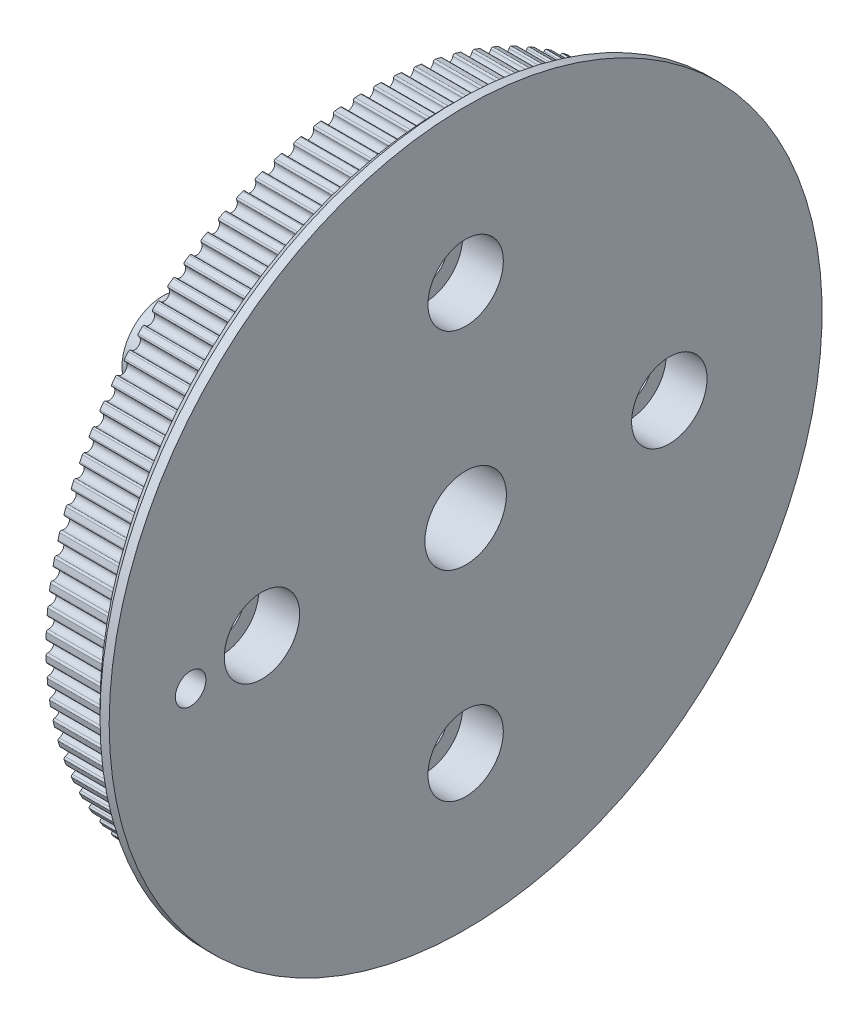
SolidWorks part; units mm, degrees
ref_plane "Front Plane" through (0, 0, 0) normal (0, 0, 1) x (1, 0, 0)
ref_plane "Top Plane" through (0, 0, 0) normal (0, 1, 0) x (1, 0, 0)
ref_plane "Right Plane" through (0, 0, 0) normal (1, 0, 0) x (0, 0, -1)
sketch "Sketch1" plane through (0, 0, 0) normal (1, 0, 0) x (0, 0, -1)
  circle A0 centre (0, 0) radius 31.6
  circle A1 centre (0, 0) radius 4
  dimension "D1" = 63.2
  dimension "D2" = 8
extrude "Boss-Extrude1" add sketch "Sketch1" along normal blind 7.7
sketch "Sketch2" plane through (0, 0, 0) normal (1, 0, 0) x (0, 0, -1)
  circle A0 centre (0, 0) radius 31.39 construction
  circle A1 centre (0, 31.39) radius 0.55
  circle A2 centre (0, 0) radius 31.39 construction
  circle A3 centre (1.971, 31.3281) radius 0.55
  circle A4 centre (0, 0) radius 31.39 construction
  circle A5 centre (3.9342, 31.1425) radius 0.55
  circle A6 centre (0, 0) radius 31.39 construction
  circle A7 centre (5.8819, 30.834) radius 0.55
  circle A8 centre (0, 0) radius 31.39 construction
  circle A9 centre (7.8064, 30.4038) radius 0.55
  circle A10 centre (0, 0) radius 31.39 construction
  circle A11 centre (9.7, 29.8537) radius 0.55
  circle A12 centre (0, 0) radius 31.39 construction
  circle A13 centre (11.5554, 29.1857) radius 0.55
  circle A14 centre (0, 0) radius 31.39 construction
  circle A15 centre (13.3652, 28.4025) radius 0.55
  circle A16 centre (0, 0) radius 31.39 construction
  circle A17 centre (15.1222, 27.5073) radius 0.55
  circle A18 centre (0, 0) radius 31.39 construction
  circle A19 centre (16.8196, 26.5035) radius 0.55
  circle A20 centre (0, 0) radius 31.39 construction
  circle A21 centre (18.4506, 25.395) radius 0.55
  circle A22 centre (0, 0) radius 31.39 construction
  circle A23 centre (20.0087, 24.1864) radius 0.55
  circle A24 centre (0, 0) radius 31.39 construction
  circle A25 centre (21.4879, 22.8823) radius 0.55
  circle A26 centre (0, 0) radius 31.39 construction
  circle A27 centre (22.8823, 21.4879) radius 0.55
  circle A28 centre (0, 0) radius 31.39 construction
  circle A29 centre (24.1864, 20.0087) radius 0.55
  circle A30 centre (0, 0) radius 31.39 construction
  circle A31 centre (25.395, 18.4506) radius 0.55
  circle A32 centre (0, 0) radius 31.39 construction
  circle A33 centre (26.5035, 16.8196) radius 0.55
  circle A34 centre (0, 0) radius 31.39 construction
  circle A35 centre (27.5073, 15.1222) radius 0.55
  circle A36 centre (0, 0) radius 31.39 construction
  circle A37 centre (28.4025, 13.3652) radius 0.55
  circle A38 centre (0, 0) radius 31.39 construction
  circle A39 centre (29.1857, 11.5554) radius 0.55
  circle A40 centre (0, 0) radius 31.39 construction
  circle A41 centre (29.8537, 9.7) radius 0.55
  circle A42 centre (0, 0) radius 31.39 construction
  circle A43 centre (30.4038, 7.8064) radius 0.55
  circle A44 centre (0, 0) radius 31.39 construction
  circle A45 centre (30.834, 5.8819) radius 0.55
  circle A46 centre (0, 0) radius 31.39 construction
  circle A47 centre (31.1425, 3.9342) radius 0.55
  circle A48 centre (0, 0) radius 31.39 construction
  circle A49 centre (31.3281, 1.971) radius 0.55
  circle A50 centre (0, 0) radius 31.39 construction
  circle A51 centre (31.39, 0) radius 0.55
  circle A52 centre (0, 0) radius 31.39 construction
  circle A53 centre (31.3281, -1.971) radius 0.55
  circle A54 centre (0, 0) radius 31.39 construction
  circle A55 centre (31.1425, -3.9342) radius 0.55
  circle A56 centre (0, 0) radius 31.39 construction
  circle A57 centre (30.834, -5.8819) radius 0.55
  circle A58 centre (0, 0) radius 31.39 construction
  circle A59 centre (30.4038, -7.8064) radius 0.55
  circle A60 centre (0, 0) radius 31.39 construction
  circle A61 centre (29.8537, -9.7) radius 0.55
  circle A62 centre (0, 0) radius 31.39 construction
  circle A63 centre (29.1857, -11.5554) radius 0.55
  circle A64 centre (0, 0) radius 31.39 construction
  circle A65 centre (28.4025, -13.3652) radius 0.55
  circle A66 centre (0, 0) radius 31.39 construction
  circle A67 centre (27.5073, -15.1222) radius 0.55
  circle A68 centre (0, 0) radius 31.39 construction
  circle A69 centre (26.5035, -16.8196) radius 0.55
  circle A70 centre (0, 0) radius 31.39 construction
  circle A71 centre (25.395, -18.4506) radius 0.55
  circle A72 centre (0, 0) radius 31.39 construction
  circle A73 centre (24.1864, -20.0087) radius 0.55
  circle A74 centre (0, 0) radius 31.39 construction
  circle A75 centre (22.8823, -21.4879) radius 0.55
  circle A76 centre (0, 0) radius 31.39 construction
  circle A77 centre (21.4879, -22.8823) radius 0.55
  circle A78 centre (0, 0) radius 31.39 construction
  circle A79 centre (20.0087, -24.1864) radius 0.55
  circle A80 centre (0, 0) radius 31.39 construction
  circle A81 centre (18.4506, -25.395) radius 0.55
  circle A82 centre (0, 0) radius 31.39 construction
  circle A83 centre (16.8196, -26.5035) radius 0.55
  circle A84 centre (0, 0) radius 31.39 construction
  circle A85 centre (15.1222, -27.5073) radius 0.55
  circle A86 centre (0, 0) radius 31.39 construction
  circle A87 centre (13.3652, -28.4025) radius 0.55
  circle A88 centre (0, 0) radius 31.39 construction
  circle A89 centre (11.5554, -29.1857) radius 0.55
  circle A90 centre (0, 0) radius 31.39 construction
  circle A91 centre (9.7, -29.8537) radius 0.55
  circle A92 centre (0, 0) radius 31.39 construction
  circle A93 centre (7.8064, -30.4038) radius 0.55
  circle A94 centre (0, 0) radius 31.39 construction
  circle A95 centre (5.8819, -30.834) radius 0.55
  circle A96 centre (0, 0) radius 31.39 construction
  circle A97 centre (3.9342, -31.1425) radius 0.55
  circle A98 centre (0, 0) radius 31.39 construction
  circle A99 centre (1.971, -31.3281) radius 0.55
  circle A100 centre (0, 0) radius 31.39 construction
  circle A101 centre (0, -31.39) radius 0.55
  circle A102 centre (0, 0) radius 31.39 construction
  circle A103 centre (-1.971, -31.3281) radius 0.55
  circle A104 centre (0, 0) radius 31.39 construction
  circle A105 centre (-3.9342, -31.1425) radius 0.55
  circle A106 centre (0, 0) radius 31.39 construction
  circle A107 centre (-5.8819, -30.834) radius 0.55
  circle A108 centre (0, 0) radius 31.39 construction
  circle A109 centre (-7.8064, -30.4038) radius 0.55
  circle A110 centre (0, 0) radius 31.39 construction
  circle A111 centre (-9.7, -29.8537) radius 0.55
  circle A112 centre (0, 0) radius 31.39 construction
  circle A113 centre (-11.5554, -29.1857) radius 0.55
  circle A114 centre (0, 0) radius 31.39 construction
  circle A115 centre (-13.3652, -28.4025) radius 0.55
  circle A116 centre (0, 0) radius 31.39 construction
  circle A117 centre (-15.1222, -27.5073) radius 0.55
  circle A118 centre (0, 0) radius 31.39 construction
  circle A119 centre (-16.8196, -26.5035) radius 0.55
  circle A120 centre (0, 0) radius 31.39 construction
  circle A121 centre (-18.4506, -25.395) radius 0.55
  circle A122 centre (0, 0) radius 31.39 construction
  circle A123 centre (-20.0087, -24.1864) radius 0.55
  circle A124 centre (0, 0) radius 31.39 construction
  circle A125 centre (-21.4879, -22.8823) radius 0.55
  circle A126 centre (0, 0) radius 31.39 construction
  circle A127 centre (-22.8823, -21.4879) radius 0.55
  circle A128 centre (0, 0) radius 31.39 construction
  circle A129 centre (-24.1864, -20.0087) radius 0.55
  circle A130 centre (0, 0) radius 31.39 construction
  circle A131 centre (-25.395, -18.4506) radius 0.55
  circle A132 centre (0, 0) radius 31.39 construction
  circle A133 centre (-26.5035, -16.8196) radius 0.55
  circle A134 centre (0, 0) radius 31.39 construction
  circle A135 centre (-27.5073, -15.1222) radius 0.55
  circle A136 centre (0, 0) radius 31.39 construction
  circle A137 centre (-28.4025, -13.3652) radius 0.55
  circle A138 centre (0, 0) radius 31.39 construction
  circle A139 centre (-29.1857, -11.5554) radius 0.55
  circle A140 centre (0, 0) radius 31.39 construction
  circle A141 centre (-29.8537, -9.7) radius 0.55
  circle A142 centre (0, 0) radius 31.39 construction
  circle A143 centre (-30.4038, -7.8064) radius 0.55
  circle A144 centre (0, 0) radius 31.39 construction
  circle A145 centre (-30.834, -5.8819) radius 0.55
  circle A146 centre (0, 0) radius 31.39 construction
  circle A147 centre (-31.1425, -3.9342) radius 0.55
  circle A148 centre (0, 0) radius 31.39 construction
  circle A149 centre (-31.3281, -1.971) radius 0.55
  circle A150 centre (0, 0) radius 31.39 construction
  circle A151 centre (-31.39, 0) radius 0.55
  circle A152 centre (0, 0) radius 31.39 construction
  circle A153 centre (-31.3281, 1.971) radius 0.55
  circle A154 centre (0, 0) radius 31.39 construction
  circle A155 centre (-31.1425, 3.9342) radius 0.55
  circle A156 centre (0, 0) radius 31.39 construction
  circle A157 centre (-30.834, 5.8819) radius 0.55
  circle A158 centre (0, 0) radius 31.39 construction
  circle A159 centre (-30.4038, 7.8064) radius 0.55
  circle A160 centre (0, 0) radius 31.39 construction
  circle A161 centre (-29.8537, 9.7) radius 0.55
  circle A162 centre (0, 0) radius 31.39 construction
  circle A163 centre (-29.1857, 11.5554) radius 0.55
  circle A164 centre (0, 0) radius 31.39 construction
  circle A165 centre (-28.4025, 13.3652) radius 0.55
  circle A166 centre (0, 0) radius 31.39 construction
  circle A167 centre (-27.5073, 15.1222) radius 0.55
  circle A168 centre (0, 0) radius 31.39 construction
  circle A169 centre (-26.5035, 16.8196) radius 0.55
  circle A170 centre (0, 0) radius 31.39 construction
  circle A171 centre (-25.395, 18.4506) radius 0.55
  circle A172 centre (0, 0) radius 31.39 construction
  circle A173 centre (-24.1864, 20.0087) radius 0.55
  circle A174 centre (0, 0) radius 31.39 construction
  circle A175 centre (-22.8823, 21.4879) radius 0.55
  circle A176 centre (0, 0) radius 31.39 construction
  circle A177 centre (-21.4879, 22.8823) radius 0.55
  circle A178 centre (0, 0) radius 31.39 construction
  circle A179 centre (-20.0087, 24.1864) radius 0.55
  circle A180 centre (0, 0) radius 31.39 construction
  circle A181 centre (-18.4506, 25.395) radius 0.55
  circle A182 centre (0, 0) radius 31.39 construction
  circle A183 centre (-16.8196, 26.5035) radius 0.55
  circle A184 centre (0, 0) radius 31.39 construction
  circle A185 centre (-15.1222, 27.5073) radius 0.55
  circle A186 centre (0, 0) radius 31.39 construction
  circle A187 centre (-13.3652, 28.4025) radius 0.55
  circle A188 centre (0, 0) radius 31.39 construction
  circle A189 centre (-11.5554, 29.1857) radius 0.55
  circle A190 centre (0, 0) radius 31.39 construction
  circle A191 centre (-9.7, 29.8537) radius 0.55
  circle A192 centre (0, 0) radius 31.39 construction
  circle A193 centre (-7.8064, 30.4038) radius 0.55
  circle A194 centre (0, 0) radius 31.39 construction
  circle A195 centre (-5.8819, 30.834) radius 0.55
  circle A196 centre (0, 0) radius 31.39 construction
  circle A197 centre (-3.9342, 31.1425) radius 0.55
  circle A198 centre (0, 0) radius 31.39 construction
  circle A199 centre (-1.971, 31.3281) radius 0.55
  point P305 (0, 0)
  dimension "D1" = 62.78
  dimension "D2" = 1.1
  dimension "D3" = 100
extrude "Cut-Extrude1" cut sketch "Sketch2" along normal up to surface (7.7 mm away) up to face at (7.7, 0, -31.6)
fillet "Fillet1" radius 0.16 200 edges at (3.85, 31.5959, 0.51) (3.85, 31.5656, 1.4749) (3.85, 21.2571, -23.3815) (3.85, 22.6833, -22.0007) (3.85, 22.0007, -22.6833) (3.85, 20.5329, -24.02) (3.85, 19.747, -24.6701) (3.85, 18.9842, -25.2618) (3.85, 18.159, -25.8614) (3.85, 17.3605, -26.404) (3.85, 16.4993, -26.9506) (3.85, 15.6684, -27.442) (3.85, 14.7745, -27.9334) (3.85, 13.9143, -28.3717) (3.85, 12.9914, -28.806) (3.85, 12.1054, -29.1894) (3.85, 23.3815, -21.2571) (3.85, 24.02, -20.5329) (3.85, 24.6701, -19.747) (3.85, 25.2618, -18.9842) (3.85, 25.8614, -18.159) (3.85, 26.404, -17.3605) (3.85, 26.9506, -16.4993) (3.85, 27.442, -15.6684) (3.85, 27.9334, -14.7745) (3.85, 28.3717, -13.9143) (3.85, 28.806, -12.9914) (3.85, 29.1894, -12.1054) (3.85, 29.5649, -11.157) (3.85, 29.8919, -10.2487) (3.85, 30.2071, -9.2786) (3.85, 30.4764, -8.3516) (3.85, 30.7301, -7.3636) (3.85, 30.9407, -6.4215) (3.85, 31.1318, -5.4195) (3.85, 31.2828, -4.466) (3.85, 31.4107, -3.454) (3.85, 31.5015, -2.4929) (3.85, 31.5656, -1.4749) (3.85, 31.5959, -0.51) (3.85, 31.5015, 2.4929) (3.85, 31.4107, 3.454) (3.85, 31.2828, 4.466) (3.85, 31.1318, 5.4195) (3.85, 30.9407, 6.4215) (3.85, 30.7301, 7.3636) (3.85, 30.4764, 8.3516) (3.85, 30.2071, 9.2786) (3.85, 29.8919, 10.2487) (3.85, 29.5649, 11.157) (3.85, 29.1894, 12.1054) (3.85, 28.806, 12.9914) (3.85, 28.3717, 13.9143) (3.85, 27.9334, 14.7745) (3.85, 27.442, 15.6684) (3.85, 26.9506, 16.4993) (3.85, 26.404, 17.3605) (3.85, 25.8614, 18.159) (3.85, 25.2618, 18.9842) (3.85, 24.6701, 19.747) (3.85, 24.02, 20.5329) (3.85, 23.3815, 21.2571) (3.85, 22.6833, 22.0007) (3.85, 22.0007, 22.6833) (3.85, 21.2571, 23.3815) (3.85, 20.5329, 24.02) (3.85, 19.747, 24.6701) (3.85, 18.9842, 25.2618) (3.85, 18.159, 25.8614) (3.85, 17.3605, 26.404) (3.85, 16.4993, 26.9506) (3.85, 15.6684, 27.442) (3.85, 14.7745, 27.9334) (3.85, 13.9143, 28.3717) (3.85, 12.9914, 28.806) (3.85, 12.1054, 29.1894) (3.85, 11.157, 29.5649) (3.85, 10.2487, 29.8919) (3.85, 9.2786, 30.2071) (3.85, 8.3516, 30.4764) (3.85, 7.3636, 30.7301) (3.85, 6.4215, 30.9407) (3.85, 5.4195, 31.1318) (3.85, 4.466, 31.2828) (3.85, 3.454, 31.4107) (3.85, 2.4929, 31.5015) (3.85, 1.4749, 31.5656) (3.85, 0.51, 31.5959) (3.85, -0.51, 31.5959) (3.85, -1.4749, 31.5656) (3.85, -2.4929, 31.5015) (3.85, -3.454, 31.4107) (3.85, -4.466, 31.2828) (3.85, -5.4195, 31.1318) (3.85, -6.4215, 30.9407) (3.85, -7.3636, 30.7301) (3.85, -8.3516, 30.4764) (3.85, -9.2786, 30.2071) (3.85, -10.2487, 29.8919) (3.85, -11.157, 29.5649) (3.85, -12.1054, 29.1894) (3.85, -12.9914, 28.806) (3.85, -13.9143, 28.3717) (3.85, -14.7745, 27.9334) (3.85, -15.6684, 27.442) (3.85, -16.4993, 26.9506) (3.85, -17.3605, 26.404) (3.85, -18.159, 25.8614) (3.85, -18.9842, 25.2618) (3.85, -19.747, 24.6701) (3.85, -20.5329, 24.02) (3.85, -21.2571, 23.3815) (3.85, -22.0007, 22.6833) (3.85, -22.6833, 22.0007) (3.85, -23.3815, 21.2571) (3.85, -24.02, 20.5329) (3.85, -24.6701, 19.747) (3.85, -25.2618, 18.9842) (3.85, -25.8614, 18.159) (3.85, -26.404, 17.3605) (3.85, -26.9506, 16.4993) (3.85, -27.442, 15.6684) (3.85, -27.9334, 14.7745) (3.85, -28.3717, 13.9143) (3.85, -28.806, 12.9914) (3.85, -29.1894, 12.1054) (3.85, -29.5649, 11.157) (3.85, -29.8919, 10.2487) (3.85, -30.2071, 9.2786) (3.85, -30.4764, 8.3516) (3.85, -30.7301, 7.3636) (3.85, -30.9407, 6.4215) (3.85, -31.1318, 5.4195) (3.85, -31.2828, 4.466) (3.85, -31.4107, 3.454) (3.85, -31.5015, 2.4929) (3.85, -31.5656, 1.4749) (3.85, -31.5959, 0.51) (3.85, -31.5959, -0.51) (3.85, -31.5656, -1.4749) (3.85, -31.5015, -2.4929) (3.85, -31.4107, -3.454) (3.85, -31.2828, -4.466) (3.85, -31.1318, -5.4195) (3.85, -30.9407, -6.4215) (3.85, -30.7301, -7.3636) (3.85, -30.4764, -8.3516) (3.85, -30.2071, -9.2786) (3.85, -29.8919, -10.2487) (3.85, -29.5649, -11.157) (3.85, -29.1894, -12.1054) (3.85, -28.806, -12.9914) (3.85, -28.3717, -13.9143) (3.85, -27.9334, -14.7745) (3.85, -27.442, -15.6684) (3.85, -26.9506, -16.4993) (3.85, -26.404, -17.3605) (3.85, -25.8614, -18.159) (3.85, -25.2618, -18.9842) (3.85, -24.6701, -19.747) (3.85, -24.02, -20.5329) (3.85, -23.3815, -21.2571) (3.85, -22.6833, -22.0007) (3.85, -22.0007, -22.6833) (3.85, -21.2571, -23.3815) (3.85, -20.5329, -24.02) (3.85, -19.747, -24.6701) (3.85, -18.9842, -25.2618) (3.85, -18.159, -25.8614) (3.85, -17.3605, -26.404) (3.85, -16.4993, -26.9506) (3.85, -15.6684, -27.442) (3.85, -14.7745, -27.9334) (3.85, -13.9143, -28.3717) (3.85, -12.9914, -28.806) (3.85, -12.1054, -29.1894) (3.85, -11.157, -29.5649) (3.85, -10.2487, -29.8919) (3.85, -9.2786, -30.2071) (3.85, -8.3516, -30.4764) (3.85, -7.3636, -30.7301) (3.85, -6.4215, -30.9407) (3.85, -5.4195, -31.1318) (3.85, -4.466, -31.2828) (3.85, -3.454, -31.4107) (3.85, -2.4929, -31.5015) (3.85, 11.157, -29.5649) (3.85, 10.2487, -29.8919) (3.85, 9.2786, -30.2071) (3.85, 8.3516, -30.4764) (3.85, 7.3636, -30.7301) (3.85, 6.4215, -30.9407) (3.85, 5.4195, -31.1318) (3.85, 4.466, -31.2828) (3.85, 3.454, -31.4107) (3.85, 2.4929, -31.5015) (3.85, 1.4749, -31.5656) (3.85, 0.51, -31.5959) (3.85, -1.4749, -31.5656) (3.85, -0.51, -31.5959)
ref_axis "Axis1" through (7.7, 0, 0) along (-1, 0, 0)
sketch "Sketch3" plane through (7.7, 0, 0) normal (1, 0, 0) x (0, 0, -1)
  circle A0 centre (0, 0) radius 35
  circle A1 centre (0, 0) radius 4
  dimension "D1" = 70
  dimension "D2" = 8
extrude "Boss-Extrude2" add sketch "Sketch3" along normal blind 1.9
sketch "Sketch6" plane through (9.6, 0, 0) normal (1, 0, 0) x (0, 0, -1)
  circle A0 centre (0, -20) radius 2.2
  circle A3 centre (-20, 0) radius 2.2
  circle A4 centre (0, 20) radius 2.2
  circle A5 centre (20, 0) radius 2.2
  point P13 (0, 0)
  dimension "D1" = 4.4
  dimension "D2" = 20
  dimension "D3" = 4
extrude "Cut-Extrude6" cut sketch "Sketch6" against normal up to surface (9.6 mm away) up to face at (0, 0, 0)
sketch "Sketch5" plane through (0, 0, 0) normal (-1, 0, 0) x (0, 0, 1)
  line L0 (0, 0) -> (-23.2202, 0) construction
  line L1 (0, 0) -> (-20.9838, -20.9838) construction
  circle A0 centre (-14.1421, -14.1421) radius 4
  circle A1 centre (-14.1421, 14.1421) radius 4
  circle A2 centre (14.1421, 14.1421) radius 4
  circle A3 centre (14.1421, -14.1421) radius 4
  point P15 (0, 0)
  dimension "D3" = 8
  dimension "D1" = 45
  dimension "D2" = 20
  dimension "D4" = 4
sketch "Sketch7" plane through (9.6, 0, 0) normal (1, 0, 0) x (0, 0, -1)
  circle A0 centre (0, -20) radius 3.7
  circle A1 centre (-20, 0) radius 3.7
  circle A2 centre (0, 20) radius 3.7
  circle A3 centre (20, 0) radius 3.7
  point P12 (0, 0)
  dimension "D1" = 7.4
  dimension "D2" = 4
extrude "Cut-Extrude4" cut sketch "Sketch7" against normal blind 4
chamfer "Chamfer1" distance 1 angle 45 1 edges at (7.7, 0, -35)
extrude "Boss-Extrude3" add sketch "Sketch5" along normal blind 6
sketch "Sketch8" plane through (9.6, 0, 0) normal (1, 0, 0) x (0, 0, -1)
  circle A0 centre (-27, -1) radius 1.5
  dimension "D1" = 3
  dimension "D2" = 1
  dimension "D3" = 27
extrude "Cut-Extrude7" cut sketch "Sketch8" against normal up to surface (9.6 mm away) up to face at (0, -14.1421, 10.1421)
